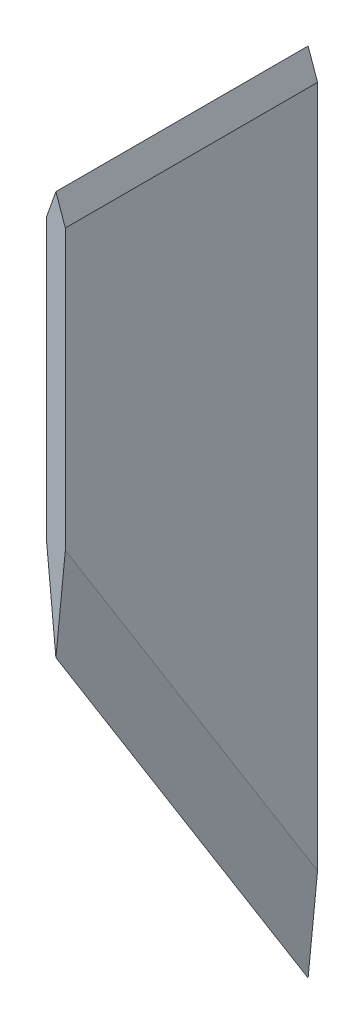
SolidWorks part; units mm, degrees
ref_plane "Front Plane" through (0, 0, 0) normal (1, 0, 0) x (0, 1, 0)
ref_plane "Top Plane" through (0, 0, 0) normal (0, 0, 1) x (0, 1, 0)
ref_plane "Right Plane" through (0, 0, 0) normal (0, 1, 0) x (-1, 0, 0)
sketch "Sketch1" plane through (0, 0, 0) normal (1, 0, 0) x (0, 1, 0)
  line L0 (0, 0) -> (203.2, 0)
  line L1 (203.2, 0) -> (203.2, 63.5)
  line L2 (203.2, 63.5) -> (101.6, 63.5)
  line L3 (101.6, 63.5) -> (0, 0)
  dimension "D1" = 203.2
  dimension "D2" = 101.6
  dimension "D3" = 63.5
  dimension "D4" = 101.6
extrude "Boss-Extrude1" add sketch "Sketch1" along normal blind 4.7625
ref_plane "Plane1" through (0, 101.6, 63.5) normal (0, 0.848, 0.53) x (-1, 0, 0)
sketch "Sketch2" plane through (0, 101.6, 63.5) normal (0, 0.848, 0.53) x (-1, 0, 0)
  line L0 (-4.7625, -13.0256) -> (-4.7625, 1.506)
  line L1 (-4.7625, 1.506) -> (0, 1.506)
  line L2 (0, -53.8479) -> (0, 0) construction
  line L3 (0, -13.0256) -> (-2.3812, 0)
  line L4 (-2.3812, 0) -> (-4.7625, -13.0256)
  line L5 (-4.7625, -53.8479) -> (-4.7625, 0) construction
  line L6 (0, 1.506) -> (0, -13.0256)
  line L7 (-4.7625, 0) -> (0, 0) construction
  point P0 (0, -2.1213)
  dimension "D1" = 20.72
extrude "Cut-Extrude1" cut sketch "Sketch2" against normal through all both and the other way through all
sketch "Sketch3" plane through (0, 0, 63.5) normal (0, 0, 1) x (1, 0, 0)
  line L0 (0, 196.4606) -> (2.3813, 203.2)
  line L1 (0, 203.2) -> (0, 126.1767) construction
  line L2 (4.7625, 203.2) -> (0, 203.2) construction
  line L3 (2.3813, 203.2) -> (4.7625, 196.4606)
  line L4 (4.7625, 203.2) -> (4.7625, 126.1767) construction
  line L5 (4.7625, 196.4606) -> (4.7625, 209.77)
  line L6 (4.7625, 209.77) -> (0, 209.77)
  line L7 (0, 209.77) -> (0, 196.4606)
  point P11 (0, 199.3622)
  point P12 (0, 0)
  point P13 (0, 0)
  point P14 (0, 209.77)
  dimension "D1" = 38.92
extrude "Cut-Extrude2" cut sketch "Sketch3" against normal through all both and the other way through all
